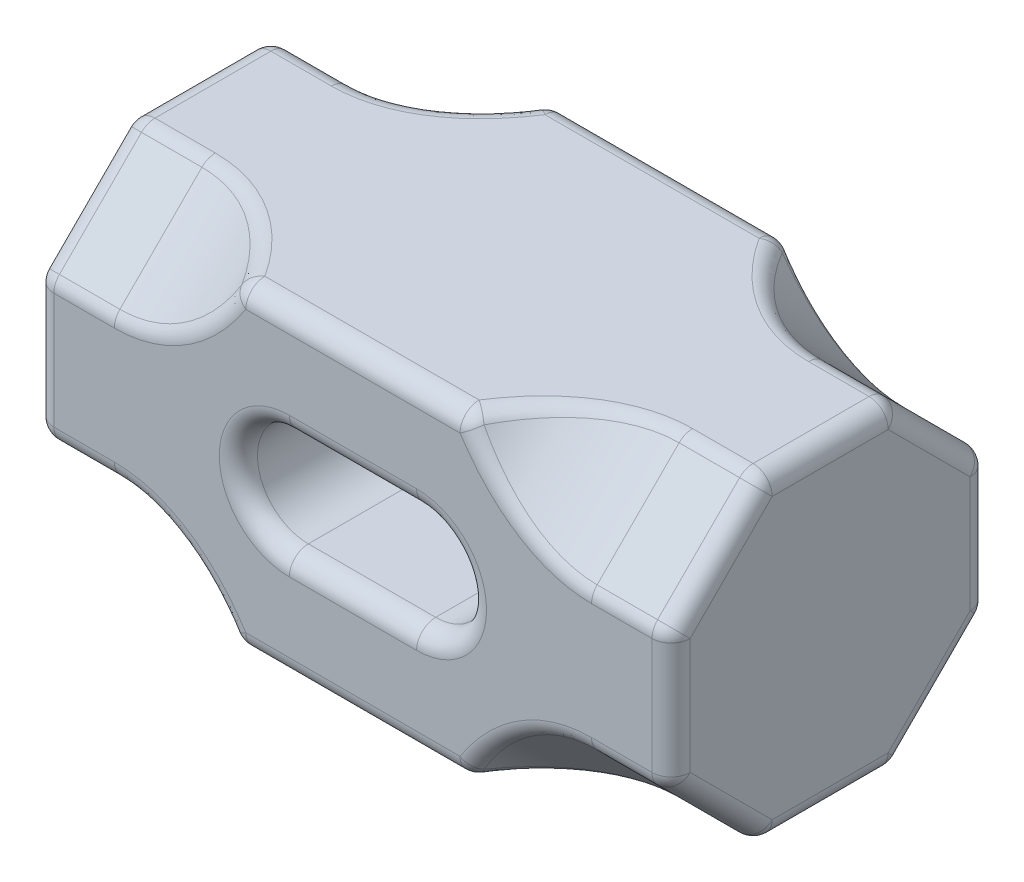
SolidWorks part; units mm, degrees
material "Gray Cast Iron"
ref_plane "Front Plane" through (0, 0, 0) normal (0, 0, 1) x (1, 0, 0)
ref_plane "Top Plane" through (0, 0, 0) normal (0, 1, 0) x (1, 0, 0)
ref_plane "Right Plane" through (0, 0, 0) normal (1, 0, 0) x (0, 0, -1)
sketch "Sketch2" plane through (0, 0, 0) normal (0, 0, 1) x (1, 0, 0)
  line L0 (-10, 0) -> (10, 0) construction
  line L1 (-50, 25) -> (50, 25)
  line L2 (-50, 25) -> (-50, -25)
  line L3 (-50, -25) -> (50, -25)
  line L4 (50, 25) -> (50, -25)
  line L5 (-50, 25) -> (50, -25) construction
  line L6 (-50, -25) -> (50, 25) construction
  line L7 (-10, 8) -> (10, 8)
  line L8 (-10, -8) -> (10, -8)
  arc A0 (-10, 8) -> (-10, -8) centre (-10, 0) ccw
  arc A1 (10, -8) -> (10, 8) centre (10, 0) ccw
  point P0 (0, 0)
  point P8 (0, 0)
  dimension "D1" = 16
  dimension "D2" = 20
  dimension "D3" = 100
  dimension "D4" = 50
extrude "Boss-Extrude1" add sketch "Sketch2" along normal blind 50
ref_plane "Plane1" through (0, -12.5, 12.5) normal (0, -0.7071, 0.7071) x (1, 0, 0)
sketch "Sketch3" plane through (0, -12.5, 12.5) normal (0, -0.7071, 0.7071) x (1, 0, 0)
  line L0 (-50, 42.6777) -> (-50, 53.033)
  line L1 (-50, 53.033) -> (-50, 17.6777) construction
  line L2 (-50, 53.033) -> (-17.2384, 53.033)
  line L3 (50, 53.033) -> (-50, 53.033) construction
  line L4 (-50, 42.6777) -> (-37.5, 42.6777)
  line L5 (-50, 17.6777) -> (-60.3297, 17.6777) construction
  line L6 (-50, -7.3223) -> (-37.5, -7.3223)
  line L7 (-50, -17.6777) -> (-17.2384, -17.6777)
  line L8 (-50, -7.3223) -> (-50, -17.6777)
  line L9 (0, 17.6777) -> (0, -25.8586) construction
  line L10 (-50, 17.6777) -> (50, 17.6777) construction
  line L11 (50, -7.3223) -> (50, -17.6777)
  line L12 (50, -17.6777) -> (17.2384, -17.6777)
  line L13 (50, -7.3223) -> (37.5, -7.3223)
  line L14 (50, 42.6777) -> (37.5, 42.6777)
  line L15 (50, 53.033) -> (17.2384, 53.033)
  line L16 (50, 42.6777) -> (50, 53.033)
  arc A0 (-17.2384, 53.033) -> (-37.5, 42.6777) centre (-37.5, 67.6777) cw
  arc A1 (-17.2384, -17.6777) -> (-37.5, -7.3223) centre (-37.5, -32.3223) ccw
  arc A2 (17.2384, -17.6777) -> (37.5, -7.3223) centre (37.5, -32.3223) cw
  arc A3 (17.2384, 53.033) -> (37.5, 42.6777) centre (37.5, 67.6777) ccw
  point P33 (0, 0)
  dimension "D1" = 25
  dimension "D2" = 12.5
  dimension "D3" = 50
extrude "Cut-Extrude1" cut sketch "Sketch3" against normal through all both and the other way through all
ref_plane "Plane2" through (0, 12.5, 12.5) normal (0, 0.7071, 0.7071) x (1, 0, 0)
ref_axis "Axis1" through (18.9622, 0, 25) along (-1, 0, 0)
pattern_circular "CirPattern1" count 4 over 360 about axis through (18.9622, 0, 25) along (-1, 0, 0) of "Cut-Extrude1"
fillet "Fillet1" radius 3 60 edges at (50, 17.6777, 42.6777) (50, 17.6777, 7.3223) (50, -17.6777, 7.3223) (50, -17.6777, 42.6777) (18, 0, 50) (0, 8, 50) (-18, 0, 50) (0, -8, 50) (-26.1228, -14.2287, 50) (-43.75, -10.3553, 50) (-43.75, 10.3553, 50) (-26.1228, 14.2287, 50) (26.1228, 14.2287, 50) (43.75, 10.3553, 50) (50, 0, 50) (43.75, -10.3553, 50) (26.1228, -14.2287, 50) (50, -25, 25) (43.75, -25, 14.6447) (26.1228, -25, 10.7713) (-26.1228, -25, 10.7713) (-43.75, -25, 14.6447) (-43.75, -25, 35.3553) (-26.1228, -25, 39.2287) (0, -25, 50) (26.1228, -25, 39.2287) (43.75, -25, 35.3553) (-50, 17.6777, 42.6777) (-50, 0, 50) (-50, -17.6777, 42.6777) (-50, -25, 25) (-50, -17.6777, 7.3223) (-50, 17.6777, 7.3223) (0, 8, 0) (18, 0, 0) (0, -8, 0) (-18, 0, 0) (-26.1228, 14.2287, 0) (-43.75, 10.3553, 0) (-50, 0, 0) (-43.75, -10.3553, 0) (-26.1228, -14.2287, 0) (0, -25, 0) (26.1228, -14.2287, 0) (43.75, -10.3553, 0) (50, 0, 0) (43.75, 10.3553, 0) (26.1228, 14.2287, 0) (50, 25, 25) (43.75, 25, 35.3553) (26.1228, 25, 39.2287) (0, 25, 50) (-26.1228, 25, 39.2287) (-43.75, 25, 35.3553) (-50, 25, 25) (-43.75, 25, 14.6447) (-26.1228, 25, 10.7713) (0, 25, 0) (26.1228, 25, 10.7713) (43.75, 25, 14.6447)
